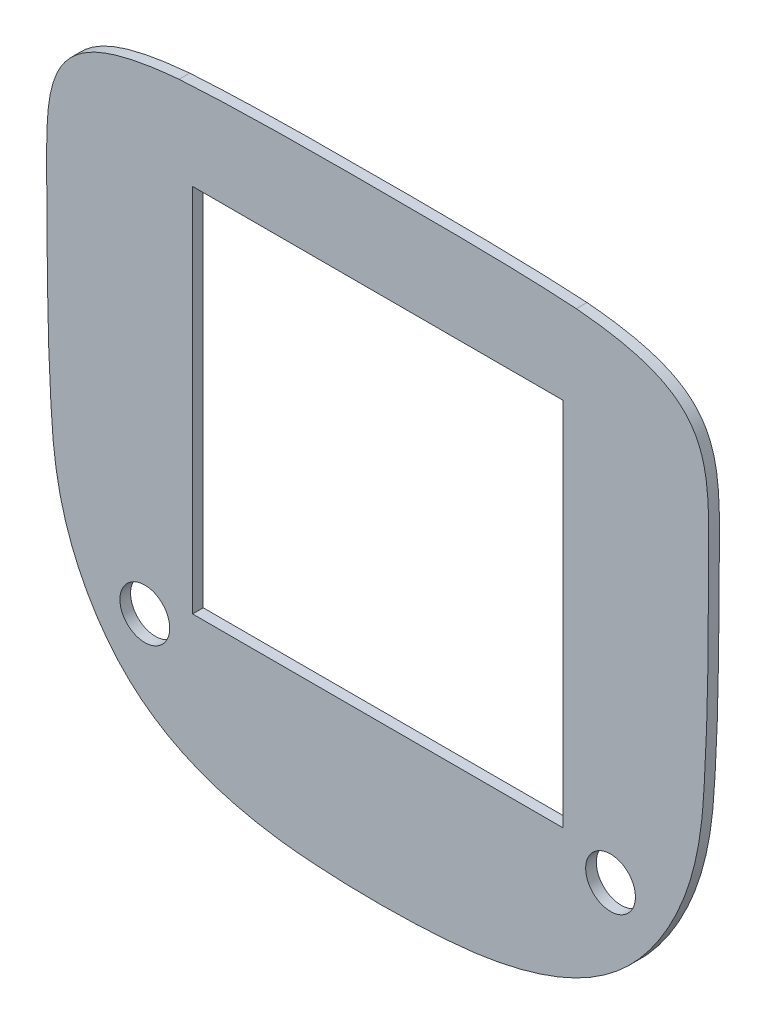
SolidWorks part; units mm, degrees
ref_plane "Front Plane" through (0, 0, 0) normal (0, 0, 1) x (1, 0, 0)
ref_plane "Top Plane" through (0, 0, 0) normal (0, 1, 0) x (1, 0, 0)
ref_plane "Right Plane" through (0, 0, 0) normal (1, 0, 0) x (0, 0, -1)
ref_plane "Plane1" through (0, 0, 100) normal (0, 0, -1) x (-1, 0, 0)
sketch "Sketch1" plane through (0, 0, 100) normal (0, 0, -1) x (-1, 0, 0)
  line L0 (0, 109.7056) -> (0, -73.1371) construction
  line L2 (-52.07, 79.9412) -> (52.07, 79.9412)
  line L3 (-52.07, 79.9412) -> (-52.07, -24.1988)
  line L4 (-52.07, -24.1988) -> (52.07, -24.1988)
  line L5 (52.07, 79.9412) -> (52.07, -24.1988)
  line L6 (-52.07, 79.9412) -> (52.07, -24.1988) construction
  line L7 (-52.07, -24.1988) -> (52.07, 79.9412) construction
  circle A0 centre (-65.5, -30.8878) radius 7
  circle A1 centre (65.5, -30.8878) radius 7
  spline S0 degree 3 poles (390.2565, 1886.8675) (296.3308, 79.582) (156.8369, -60.7899) (9.156, -68.4596) (4.5994, -68.5614) (-4.5192, -68.5626) (-9.0812, -68.4622) (-15.9299, -68.1084) (-18.2137, -67.9563) (-146.3586, -57.1836) (-285.317, 76.2796) (1445.6753, 1266.3529) knots -7.609256 -7.609256 -7.609256 -7.609256 0.25 0.25 0.5 0.5 0.75 0.75 0.875 0.875 7.760397 7.760397 7.760397 7.760397 only from (27.355, -67.0609) to (-27.355, -67.0609)
  spline S1 degree 3 poles (-383.0543, -1850.5066) (-364.9249, 28.0842) (-206.0818, 99.2449) (-37.5468, 104.943) (-32.9585, 105.0458) (-23.7809, 105.1902) (-19.1919, 105.2316) (-10.0136, 105.2808) (-5.2092, 105.2889) (-0.4047, 105.2894) (-0.1179, 105.2895) (-0.0476, 105.2895) (2.0953, 105.2894) (4.1642, 105.2881) (8.5976, 105.2806) (10.962, 105.2737) (18.055, 105.2405) (22.7834, 105.2016) (32.2392, 105.0607) (36.9665, 104.959) (207.0809, 99.3324) (374.1373, 28.0549) (90.7394, -1875.0746) knots -4.346239 -4.346239 -4.346239 -4.346239 0.125 0.125 0.25 0.25 0.375 0.375 0.5 0.505859 0.505859 0.507812 0.507812 0.5625 0.5625 0.625 0.625 0.75 0.75 0.875 0.875 5.248996 5.248996 5.248996 5.248996 only from (-55.8659, 104.1312) to (55.8659, 104.1312)
  spline S2 degree 3 poles (-55.8659, 104.1312) (-51.2933, 104.4268) (-46.7138, 104.633) (-37.5468, 104.943) (-32.9585, 105.0458) (-23.7809, 105.1902) (-19.1919, 105.2316) (-10.0136, 105.2808) (-5.2092, 105.2889) (-0.4047, 105.2894) (-0.1179, 105.2895) (-0.0476, 105.2895) (2.0953, 105.2894) (4.1642, 105.2881) (8.5976, 105.2806) (10.962, 105.2737) (18.055, 105.2405) (22.7834, 105.2016) (32.2392, 105.0607) (36.9665, 104.959) (46.4194, 104.6463) (51.1472, 104.4362) (55.8659, 104.1312) knots 0 0 0 0 0.125 0.125 0.25 0.25 0.375 0.375 0.5 0.505859 0.505859 0.507812 0.507812 0.5625 0.5625 0.625 0.625 0.75 0.75 0.875 0.875 1 1 1 1
  spline S3 degree 3 poles (27.355, -67.0609) (22.8108, -67.6157) (18.2617, -67.9867) (9.156, -68.4596) (4.5994, -68.5614) (-4.5192, -68.5626) (-9.0812, -68.4622) (-15.9299, -68.1084) (-18.2137, -67.9563) (-22.7835, -67.5721) (-25.0727, -67.3396) (-27.355, -67.0609) knots 0 0 0 0 0.25 0.25 0.5 0.5 0.75 0.75 0.875 0.875 1 1 1 1
  spline S5 degree 3 poles (56.2513, 2095.4298) (-166.2899, -11.3273) (-40.4394, 117.9123) (65.3699, 102.9931) (67.7267, 102.5852) (71.2329, 101.7869) (72.3966, 101.489) (74.7111, 100.8094) (75.8628, 100.4275) (78.1118, 99.5645) (79.2128, 99.082) (80.8185, 98.2584) (81.3461, 97.9672) (82.3838, 97.347) (82.8958, 97.0168) (84.3811, 95.975) (85.3075, 95.2102) (86.5865, 93.9414) (86.9943, 93.4982) (87.7711, 92.5688) (88.1403, 92.0818) (89.1658, 90.5883) (89.7485, 89.5389) (90.4902, 87.8946) (90.7155, 87.3349) (91.1265, 86.1944) (91.3113, 85.616) (91.8065, 83.8785) (92.0608, 82.7092) (92.467, 80.3557) (92.6189, 79.1716) (92.8517, 76.7929) (92.9326, 75.5984) (93.05, 73.203) (93.0856, 72.0013) (93.127, 69.5995) (93.1345, 68.3986) (93.1287, 65.997) (93.118, 64.7962) (93.0925, 61.1938) (93.0791, 58.7922) (93.037, 51.5874) (93.0085, 46.7842) (92.8583, 32.3749) (92.6764, 22.7684) (92.1153, 10.7733) (91.9863, 8.3749) (91.7612, 4.7807) (91.6815, 3.583) (91.5118, 1.1888) (91.4233, -0.008) (91.0907, -3.5921) (90.7896, -5.974) (90.2002, -9.5338) (89.9806, -10.7181) (89.4952, -13.0663) (89.2291, -14.232) (88.3571, -17.7029) (87.6773, -19.9818) (86.1026, -24.4629) (85.2066, -26.6647) (83.7035, -29.9107) (83.1757, -30.9831) (82.0655, -33.1086) (81.4814, -34.1641) (79.655, -37.2802) (78.3442, -39.2833) (75.52, -43.1277) (74.0056, -44.9683) (71.5576, -47.5886) (70.7123, -48.4386) (68.9597, -50.0892) (68.0499, -50.8916) (63.4108, -54.7198) (59.3665, -57.2358) (53.9772, -59.8326) (52.8825, -60.3244) (50.6611, -61.2553) (49.5364, -61.6936) (46.1427, -62.9261) (43.8466, -63.6419) (39.198, -64.8962) (36.8451, -65.4341) (-102.4759, -92.5848) (-285.6904, 136.9643) (-32.8233, -2049.1824) knots -1.333657 -1.333657 -1.333657 -1.333657 0.03125 0.03125 0.0625 0.0625 0.078125 0.078125 0.09375 0.09375 0.109375 0.109375 0.117188 0.117188 0.125 0.125 0.140625 0.140625 0.148438 0.148438 0.15625 0.15625 0.171875 0.171875 0.179688 0.179688 0.1875 0.1875 0.203125 0.203125 0.21875 0.21875 0.234375 0.234375 0.25 0.25 0.265625 0.265625 0.28125 0.28125 0.3125 0.3125 0.375 0.375 0.5 0.5 0.53125 0.53125 0.546875 0.546875 0.5625 0.5625 0.59375 0.59375 0.609375 0.609375 0.625 0.625 0.65625 0.65625 0.6875 0.6875 0.703125 0.703125 0.71875 0.71875 0.75 0.75 0.78125 0.78125 0.796875 0.796875 0.8125 0.8125 0.875 0.875 0.890625 0.890625 0.90625 0.90625 0.9375 0.9375 0.96875 0.96875 2.780112 2.780112 2.780112 2.780112 only from (55.8659, 104.1312) to (27.355, -67.0609)
  spline S12 degree 3 poles (55.8659, 104.1312) (58.2532, 103.9195) (60.6333, 103.6609) (65.3699, 102.9931) (67.7267, 102.5852) (71.2329, 101.7869) (72.3966, 101.489) (74.7111, 100.8094) (75.8628, 100.4275) (78.1118, 99.5645) (79.2128, 99.082) (80.8185, 98.2584) (81.3461, 97.9672) (82.3838, 97.347) (82.8958, 97.0168) (84.3811, 95.975) (85.3075, 95.2102) (86.5865, 93.9414) (86.9943, 93.4982) (87.7711, 92.5688) (88.1403, 92.0818) (89.1658, 90.5883) (89.7485, 89.5389) (90.4902, 87.8946) (90.7155, 87.3349) (91.1265, 86.1944) (91.3113, 85.616) (91.8065, 83.8785) (92.0608, 82.7092) (92.467, 80.3557) (92.6189, 79.1716) (92.8517, 76.7929) (92.9326, 75.5984) (93.05, 73.203) (93.0856, 72.0013) (93.127, 69.5995) (93.1345, 68.3986) (93.1287, 65.997) (93.118, 64.7962) (93.0925, 61.1938) (93.0791, 58.7922) (93.037, 51.5874) (93.0085, 46.7842) (92.8583, 32.3749) (92.6764, 22.7684) (92.1153, 10.7733) (91.9863, 8.3749) (91.7612, 4.7807) (91.6815, 3.583) (91.5118, 1.1888) (91.4233, -0.008) (91.0907, -3.5921) (90.7896, -5.974) (90.2002, -9.5338) (89.9806, -10.7181) (89.4952, -13.0663) (89.2291, -14.232) (88.3571, -17.7029) (87.6773, -19.9818) (86.1026, -24.4629) (85.2066, -26.6647) (83.7035, -29.9107) (83.1757, -30.9831) (82.0655, -33.1086) (81.4814, -34.1641) (79.655, -37.2802) (78.3442, -39.2833) (75.52, -43.1277) (74.0056, -44.9683) (71.5576, -47.5886) (70.7123, -48.4386) (68.9597, -50.0892) (68.0499, -50.8916) (63.4108, -54.7198) (59.3665, -57.2358) (53.9772, -59.8326) (52.8825, -60.3244) (50.6611, -61.2553) (49.5364, -61.6936) (46.1427, -62.9261) (43.8466, -63.6419) (39.198, -64.8962) (36.8451, -65.4341) (32.1195, -66.355) (29.7429, -66.7392) (27.355, -67.0609) knots 0 0 0 0 0.03125 0.03125 0.0625 0.0625 0.078125 0.078125 0.09375 0.09375 0.109375 0.109375 0.117188 0.117188 0.125 0.125 0.140625 0.140625 0.148438 0.148438 0.15625 0.15625 0.171875 0.171875 0.179688 0.179688 0.1875 0.1875 0.203125 0.203125 0.21875 0.21875 0.234375 0.234375 0.25 0.25 0.265625 0.265625 0.28125 0.28125 0.3125 0.3125 0.375 0.375 0.5 0.5 0.53125 0.53125 0.546875 0.546875 0.5625 0.5625 0.59375 0.59375 0.609375 0.609375 0.625 0.625 0.65625 0.65625 0.6875 0.6875 0.703125 0.703125 0.71875 0.71875 0.75 0.75 0.78125 0.78125 0.796875 0.796875 0.8125 0.8125 0.875 0.875 0.890625 0.890625 0.90625 0.90625 0.9375 0.9375 0.96875 0.96875 1 1 1 1
  spline S13 degree 3 poles (-8.2852, -2051.108) (283.697, 163.5482) (91.8272, -100.2463) (-42.6847, -63.9555) (-43.8419, -63.619) (-46.1319, -62.9003) (-47.2661, -62.5178) (-50.6334, -61.2957) (-52.8313, -60.3812) (-57.119, -58.3222) (-59.2092, -57.1785) (-62.2512, -55.2647) (-63.2496, -54.5936) (-64.7219, -53.5332) (-65.2094, -53.1701) (-66.1677, -52.4314) (-66.6393, -52.0553) (-68.96, -50.142) (-70.697, -48.5052) (-73.9483, -45.0341) (-75.4628, -43.1999) (-77.5866, -40.3172) (-78.2699, -39.3346) (-79.5898, -37.3276) (-80.2278, -36.3007) (-82.0616, -33.1784) (-83.1722, -31.0532) (-85.183, -26.7204) (-86.0835, -24.513) (-87.6676, -20.0134) (-88.3523, -17.7217) (-89.2307, -14.2259) (-89.4991, -13.0493) (-89.987, -10.6855) (-90.206, -9.5011) (-90.7943, -5.9407) (-91.0947, -3.5577) (-91.4263, 0.029) (-91.5147, 1.2269) (-91.6843, 3.6233) (-91.764, 4.8221) (-91.9888, 8.4197) (-92.1178, 10.8204) (-92.6784, 22.8314) (-92.8595, 32.4481) (-93.0092, 46.8746) (-93.0375, 51.6834) (-93.0797, 58.8965) (-93.0933, 61.3009) (-93.1188, 64.9075) (-93.1296, 66.1097) (-93.1341, 68.5141) (-93.1259, 69.7163) (-93.0826, 72.1206) (-93.0457, 73.3227) (-92.9246, 75.7269) (-92.8411, 76.9308) (-92.6007, 79.3248) (-92.4441, 80.5157) (-92.026, 82.8795) (-91.7644, 84.0525) (-91.2564, 85.7924) (-91.0682, 86.367) (-90.6528, 87.4942) (-90.4251, 88.0482) (-89.6753, 89.6779) (-89.0858, 90.7212) (-88.0451, 92.2106) (-87.6751, 92.6901) (-86.8984, 93.6048) (-86.4904, 94.0418) (-85.2103, 95.2944) (-84.2821, 96.0518) (-82.7914, 97.0857) (-82.2819, 97.4107) (-81.2485, 98.0222) (-80.7234, 98.3094) (-79.1256, 99.1218) (-78.0306, 99.5982) (-75.795, 100.4508) (-74.6518, 100.8282) (-72.3431, 101.5033) (-71.1825, 101.7993) (-67.6864, 102.5926) (-65.337, 102.9983) (40.4346, 117.8875) (165.497, -11.1437) (-46.5312, 2095.3826) knots -1.726709 -1.726709 -1.726709 -1.726709 0.0625 0.0625 0.078125 0.078125 0.09375 0.09375 0.125 0.125 0.15625 0.15625 0.171875 0.171875 0.179687 0.179687 0.1875 0.1875 0.21875 0.21875 0.25 0.25 0.265625 0.265625 0.28125 0.28125 0.3125 0.3125 0.34375 0.34375 0.375 0.375 0.390625 0.390625 0.40625 0.40625 0.4375 0.4375 0.453125 0.453125 0.46875 0.46875 0.5 0.5 0.625 0.625 0.6875 0.6875 0.71875 0.71875 0.734375 0.734375 0.75 0.75 0.765625 0.765625 0.78125 0.78125 0.796875 0.796875 0.8125 0.8125 0.820313 0.820313 0.828125 0.828125 0.84375 0.84375 0.851563 0.851563 0.859375 0.859375 0.875 0.875 0.882812 0.882812 0.890625 0.890625 0.90625 0.90625 0.921875 0.921875 0.9375 0.9375 0.96875 0.96875 2.337844 2.337844 2.337844 2.337844 only from (-27.355, -67.0609) to (-55.8659, 104.1312)
  spline S14 degree 3 poles (-27.355, -67.0609) (-32.1327, -66.4173) (-36.8622, -65.5264) (-42.6847, -63.9555) (-43.8419, -63.619) (-46.1319, -62.9003) (-47.2661, -62.5178) (-50.6334, -61.2957) (-52.8313, -60.3812) (-57.119, -58.3222) (-59.2092, -57.1785) (-62.2512, -55.2647) (-63.2496, -54.5936) (-64.7219, -53.5332) (-65.2094, -53.1701) (-66.1677, -52.4314) (-66.6393, -52.0553) (-68.96, -50.142) (-70.697, -48.5052) (-73.9483, -45.0341) (-75.4628, -43.1999) (-77.5866, -40.3172) (-78.2699, -39.3346) (-79.5898, -37.3276) (-80.2278, -36.3007) (-82.0616, -33.1784) (-83.1722, -31.0532) (-85.183, -26.7204) (-86.0835, -24.513) (-87.6676, -20.0134) (-88.3523, -17.7217) (-89.2307, -14.2259) (-89.4991, -13.0493) (-89.987, -10.6855) (-90.206, -9.5011) (-90.7943, -5.9407) (-91.0947, -3.5577) (-91.4263, 0.029) (-91.5147, 1.2269) (-91.6843, 3.6233) (-91.764, 4.8221) (-91.9888, 8.4197) (-92.1178, 10.8204) (-92.6784, 22.8314) (-92.8595, 32.4481) (-93.0092, 46.8746) (-93.0375, 51.6834) (-93.0797, 58.8965) (-93.0933, 61.3009) (-93.1188, 64.9075) (-93.1296, 66.1097) (-93.1341, 68.5141) (-93.1259, 69.7163) (-93.0826, 72.1206) (-93.0457, 73.3227) (-92.9246, 75.7269) (-92.8411, 76.9308) (-92.6007, 79.3248) (-92.4441, 80.5157) (-92.026, 82.8795) (-91.7644, 84.0525) (-91.2564, 85.7924) (-91.0682, 86.367) (-90.6528, 87.4942) (-90.4251, 88.0482) (-89.6753, 89.6779) (-89.0858, 90.7212) (-88.0451, 92.2106) (-87.6751, 92.6901) (-86.8984, 93.6048) (-86.4904, 94.0418) (-85.2103, 95.2944) (-84.2821, 96.0518) (-82.7914, 97.0857) (-82.2819, 97.4107) (-81.2485, 98.0222) (-80.7234, 98.3094) (-79.1256, 99.1218) (-78.0306, 99.5982) (-75.795, 100.4508) (-74.6518, 100.8282) (-72.3431, 101.5033) (-71.1825, 101.7993) (-67.6864, 102.5926) (-65.337, 102.9983) (-60.6162, 103.6628) (-58.2446, 103.9203) (-55.8659, 104.1312) knots 0 0 0 0 0.0625 0.0625 0.078125 0.078125 0.09375 0.09375 0.125 0.125 0.15625 0.15625 0.171875 0.171875 0.179687 0.179687 0.1875 0.1875 0.21875 0.21875 0.25 0.25 0.265625 0.265625 0.28125 0.28125 0.3125 0.3125 0.34375 0.34375 0.375 0.375 0.390625 0.390625 0.40625 0.40625 0.4375 0.4375 0.453125 0.453125 0.46875 0.46875 0.5 0.5 0.625 0.625 0.6875 0.6875 0.71875 0.71875 0.734375 0.734375 0.75 0.75 0.765625 0.765625 0.78125 0.78125 0.796875 0.796875 0.8125 0.8125 0.820313 0.820313 0.828125 0.828125 0.84375 0.84375 0.851563 0.851563 0.859375 0.859375 0.875 0.875 0.882812 0.882812 0.890625 0.890625 0.90625 0.90625 0.921875 0.921875 0.9375 0.9375 0.96875 0.96875 1 1 1 1
  point P7 (0, 27.8712)
  dimension "D1" = 14
  dimension "D2" = 104.14
  dimension "D3" = 104.14
extrude "Boss-Extrude1" add sketch "Sketch1" along normal blind 3 contours A1 A0 L2 L5 L4 L3 region at (0, -66.0141, 100)
